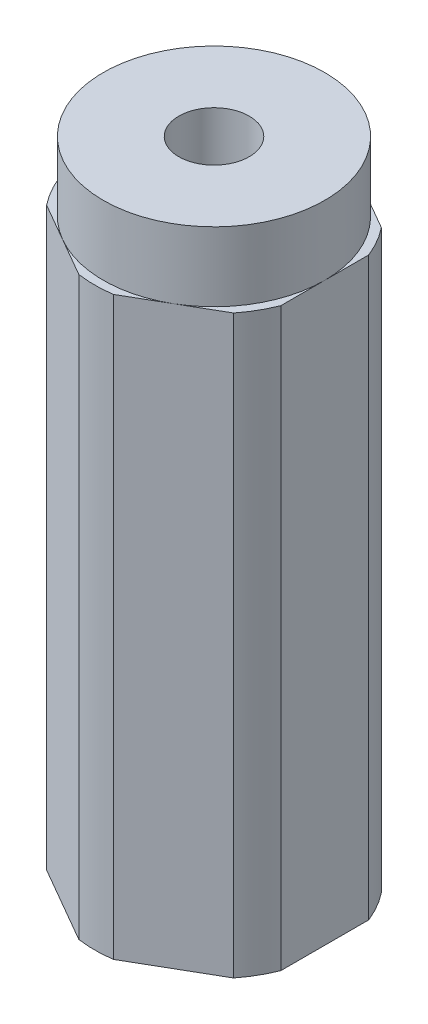
SolidWorks part; units mm, degrees
material "7075-T6 (SN)"
ref_plane "Front Plane" through (0, 0, 0) normal (0, 0, 1) x (1, 0, 0)
ref_plane "Top Plane" through (0, 0, 0) normal (0, 1, 0) x (1, 0, 0)
ref_plane "Right Plane" through (0, 0, 0) normal (1, 0, 0) x (0, 0, -1)
sketch "Sketch1" plane through (0, 0, 0) normal (0, 1, 0) x (1, 0, 0)
  line L1 (0, 7.3323) -> (-6.35, 3.6662)
  line L2 (-6.35, 3.6662) -> (-6.35, -3.6662)
  line L3 (-6.35, -3.6662) -> (0, -7.3323)
  line L4 (0, -7.3323) -> (6.35, -3.6662)
  line L5 (6.35, -3.6662) -> (6.35, 3.6662)
  line L6 (6.35, 3.6662) -> (0, 7.3323)
  circle A0 centre (0, 0) radius 6.35 construction
  circle A1 centre (0, 0) radius 6.8326
  dimension "D1" = 12.7
  dimension "D2" = 13.6652
extrude "Boss-Extrude1" add sketch "Sketch1" along normal mid plane 33.02 contours L4 A1 L5 L6 L1 L2 L3 region at (0, 0, 0)
sketch "Sketch3" plane through (0, 16.51, 0) normal (0, 1, 0) x (1, 0, 0)
  line L0 (5.3594, 4.2381) -> (0.9906, 6.7604) construction
  circle A0 centre (0, 0) radius 6.35
extrude "Boss-Extrude2" add sketch "Sketch3" along normal mid plane 7.9375
sketch "Sketch2" plane through (0, -16.51, 0) normal (0, 1, 0) x (1, 0, 0)
  circle A0 centre (0, 0) radius 2.0193
  dimension "D1" = 4.0386
extrude "Cut-Extrude1" cut sketch "Sketch2" along normal through all
